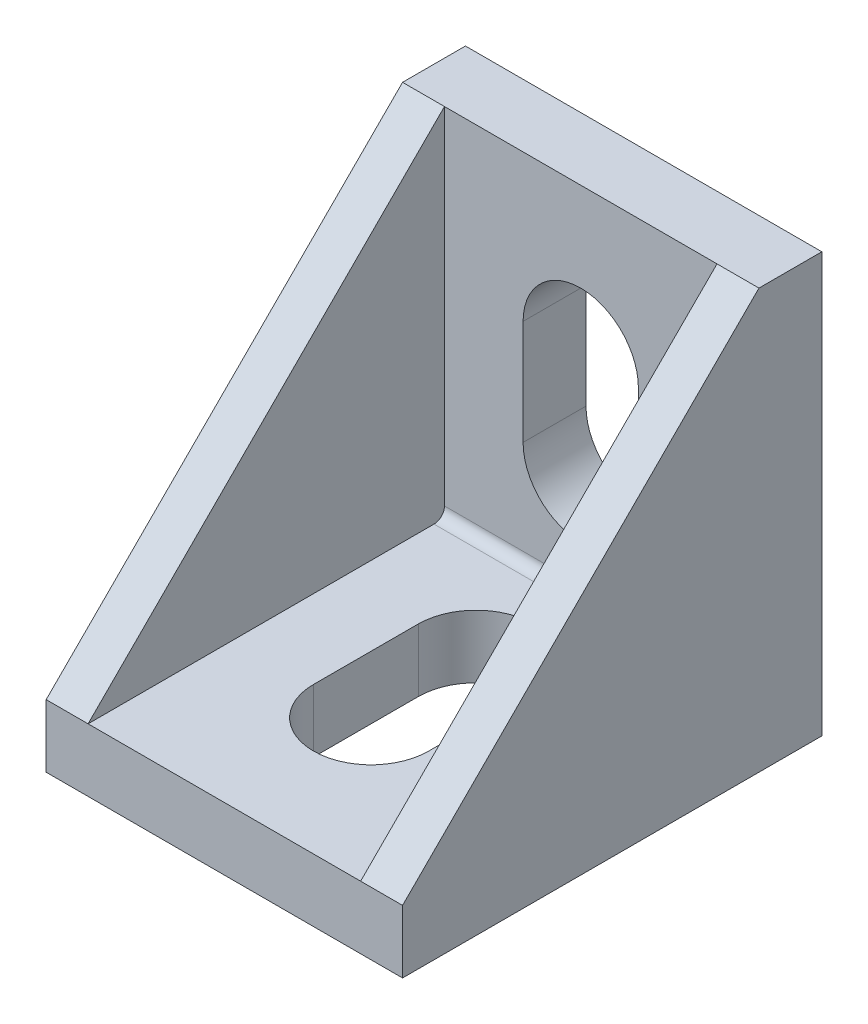
SolidWorks part; units mm, degrees
material "Zinc AG40A (Zn-4Al-0.4Mg; Zamak 3), Cast"
ref_plane "Front Plane" through (0, 0, 0) normal (0, 0, 1) x (1, 0, 0)
ref_plane "Top Plane" through (0, 0, 0) normal (0, 1, 0) x (1, 0, 0)
ref_plane "Right Plane" through (0, 0, 0) normal (1, 0, 0) x (0, 0, -1)
ref_plane "Plane1" through (8.5, 0, 0) normal (1, 0, 0) x (0, 0, -1)
sketch "Sketch16" plane through (8.5, 0, 0) normal (1, 0, 0) x (0, 0, -1)
  line L0 (-3, 3) -> (-3, 20)
  line L1 (-3, 20) -> (-20, 3)
  line L2 (-20, 3) -> (-3, 3)
  dimension "D1" = 17
  dimension "D2" = 17
extrude "Boss-Extrude1" add sketch "Sketch16" against normal blind 17
sketch "Sketch17" plane through (0, 0, 3) normal (0, 0, -1) x (-1, 0, 0)
  line L0 (-8.5, 3) -> (-8.5, 20)
  line L1 (-8.5, 20) -> (8.5, 20)
  line L2 (8.5, 20) -> (8.5, 3)
  line L3 (8.5, 3) -> (-8.5, 3)
  line L4 (-8.5, 3) -> (-8.5, 20) construction
  line L5 (8.5, 3) -> (-8.5, 3) construction
  dimension "D1" = 17
  dimension "D2" = 17
extrude "Boss-Extrude2" add sketch "Sketch17" along normal blind 3
ref_plane "Plane2" through (6.5, 0, 0) normal (1, 0, 0) x (0, 0, -1)
sketch "Sketch22" plane through (6.5, 0, 0) normal (1, 0, 0) x (0, 0, -1)
  line L0 (-3, 20) -> (-20, 3)
  line L1 (-20, 3) -> (-3, 3)
  line L2 (-3, 3) -> (-3, 20)
  dimension "D1" = 17
  dimension "D2" = 17
extrude "Cut-Extrude1" cut sketch "Sketch22" against normal blind 13
sketch "Sketch23" plane through (0, 3, 0) normal (0, -1, 0) x (1, 0, 0)
  line L0 (-8.5, 0) -> (-8.5, 20)
  line L1 (-8.5, 20) -> (8.5, 20)
  line L2 (8.5, 20) -> (8.5, 0)
  line L3 (8.5, 0) -> (-8.5, 0)
  line L4 (-8.5, 20) -> (-8.5, 0) construction
  dimension "D1" = 17
  dimension "D2" = 20
extrude "Boss-Extrude3" add sketch "Sketch23" along normal blind 3
sketch "Sketch24" plane through (0, 0, 0) normal (0, -1, 0) x (1, 0, 0)
  line L0 (6, 0) -> (6, 1)
  line L1 (6, 1) -> (-6, 1)
  line L2 (-6, 1) -> (-6, 0)
  line L3 (-6, 0) -> (6, 0)
  line L4 (8.5, 0) -> (8.5, 20) construction
  line L5 (-8.5, 0) -> (8.5, 0) construction
  dimension "D1" = 2.5
  dimension "D2" = 14.5
  dimension "D3" = 1
extrude "Cut-Extrude2" cut sketch "Sketch24" against normal blind 3
ref_plane "Plane3" through (0, 0, 3) normal (0, 0, 1) x (1, 0, 0)
sketch "Sketch30" plane through (0, 0, 3) normal (0, 0, 1) x (1, 0, 0)
  line L0 (-6, 1) -> (-6, 0)
  line L1 (-6, 0) -> (6, 0)
  line L2 (6, 0) -> (6, 1)
  line L3 (6, 1) -> (-6, 1)
  dimension "D1" = 12
  dimension "D2" = 1
ref_plane "Plane4" through (0, 0, 1) normal (0, 0, -1) x (-1, 0, 0)
extrude "Cut-Extrude3" cut sketch "Sketch30" against normal up to surface (2 mm away) up to plane "Plane4"
sketch "Sketch37" plane through (0, 0, 3) normal (0, 0, 1) x (1, 0, 0)
  line L0 (2.75, 8) -> (2.75, 13)
  line L1 (-2.75, 13) -> (-2.75, 8)
  line L2 (6.5, 3) -> (6.5, 20) construction
  line L3 (-6.5, 20) -> (6.5, 20) construction
  arc A0 (2.75, 13) -> (-2.75, 13) centre (0, 13) ccw
  arc A1 (-2.75, 8) -> (2.75, 8) centre (0, 8) ccw
  dimension "D1" = 2.75
  dimension "D2" = 6.5
  dimension "D3" = 7
  dimension "D4" = 12
extrude "Cut-Extrude4" cut sketch "Sketch37" against normal through all
sketch "Sketch38" plane through (0, 3, 0) normal (0, 1, 0) x (-1, 0, 0)
  line L0 (-2.75, 13) -> (-2.75, 8)
  line L1 (2.75, 8) -> (2.75, 13)
  line L2 (6.5, 20) -> (6.5, 3) construction
  arc A0 (2.75, 13) -> (-2.75, 13) centre (0, 13) ccw
  arc A1 (-2.75, 8) -> (2.75, 8) centre (0, 8) ccw
  dimension "D1" = 2.75
  dimension "D2" = 6.5
  dimension "D3" = 7
  dimension "D4" = 12
extrude "Cut-Extrude5" cut sketch "Sketch38" against normal through all
sketch "Sketch39" plane through (0, 0, 0) normal (0, -1, 0) x (1, 0, 0)
  line L0 (6, 19) -> (-6, 19)
  line L1 (-6, 19) -> (-6, 16)
  line L2 (-6, 16) -> (6, 16)
  line L3 (6, 16) -> (6, 19)
  line L4 (-6, 3) -> (-6, 0) construction
  line L5 (-6, 3) -> (6, 3) construction
  dimension "D1" = 12
  dimension "D2" = 13
  dimension "D3" = 16
extrude "Cut-Extrude6" cut sketch "Sketch39" against normal blind 1
sketch "Sketch40" plane through (0, 1, 0) normal (0, -1, 0) x (1, 0, 0)
  line L0 (-3, 18) -> (3, 18)
  line L1 (3, 18) -> (3, 17)
  line L2 (3, 17) -> (-3, 17)
  line L3 (-3, 17) -> (-3, 18)
  line L4 (6, 16) -> (6, 19) construction
  line L5 (6, 19) -> (-6, 19) construction
  dimension "D1" = 3
  dimension "D2" = 9
  dimension "D3" = 1
  dimension "D4" = 2
extrude "Boss-Extrude4" add sketch "Sketch40" along normal blind 2.5
sketch "Sketch41" plane through (0, 1, 0) normal (0, -1, 0) x (1, 0, 0)
  line L0 (-3, 1) -> (-3, 2)
  line L1 (-3, 2) -> (3, 2)
  line L2 (3, 2) -> (3, 1)
  line L3 (3, 1) -> (-3, 1)
  line L4 (6, 1) -> (6, 3) construction
  line L5 (6, 3) -> (-6, 3) construction
  dimension "D1" = 3
  dimension "D2" = 9
  dimension "D3" = 1
  dimension "D4" = 2
extrude "Boss-Extrude5" add sketch "Sketch41" along normal blind 2.5
ref_plane "Plane5" through (0, 0, -1.5) normal (0, 0, -1) x (-1, 0, 0)
sketch "Sketch49" plane through (0, 0, -1.5) normal (0, 0, -1) x (-1, 0, 0)
  line L0 (3, 1) -> (3, 2)
  line L1 (3, 2) -> (-3, 2)
  line L2 (-3, 2) -> (-3, 1)
  line L3 (-3, 1) -> (3, 1)
  dimension "D1" = 6
  dimension "D2" = 1
extrude "Boss-Extrude6" add sketch "Sketch49" against normal up to next
sketch "Sketch50" plane through (0, 0, 0) normal (0, 0, -1) x (-1, 0, 0)
  line L0 (-6, 16) -> (6, 16)
  line L1 (6, 16) -> (6, 19)
  line L2 (6, 19) -> (-6, 19)
  line L3 (-6, 19) -> (-6, 16)
  line L4 (6, 3) -> (6, 0) construction
  line L5 (6, 3) -> (-6, 3) construction
  dimension "D1" = 12
  dimension "D2" = 13
  dimension "D3" = 16
extrude "Cut-Extrude7" cut sketch "Sketch50" against normal blind 1
sketch "Sketch51" plane through (0, 0, 1) normal (0, 0, -1) x (-1, 0, 0)
  line L0 (3, 17) -> (-3, 17)
  line L1 (-3, 17) -> (-3, 18)
  line L2 (-3, 18) -> (3, 18)
  line L3 (3, 18) -> (3, 17)
  line L4 (-6, 19) -> (-6, 16) construction
  line L5 (-6, 16) -> (6, 16) construction
  dimension "D1" = 3
  dimension "D2" = 9
  dimension "D3" = 1
  dimension "D4" = 2
extrude "Boss-Extrude7" add sketch "Sketch51" along normal blind 2.5
fillet "Fillet1" radius 0.5 1 edges at (0, 3, 3) tangent propagation no
